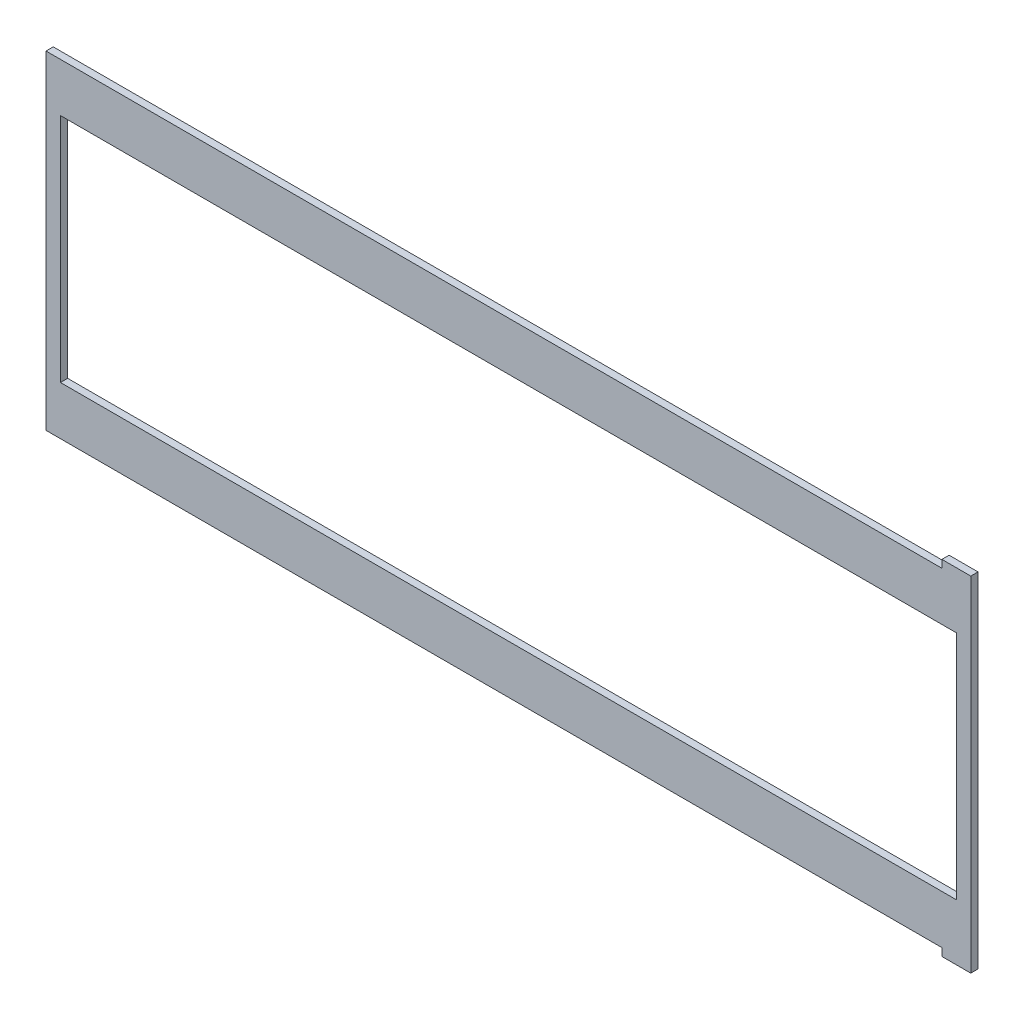
SolidWorks part; units mm, degrees
ref_plane "Front Plane" through (0, 0, 0) normal (0, 0, 1) x (1, 0, 0)
ref_plane "Top Plane" through (0, 0, 0) normal (0, 1, 0) x (1, 0, 0)
ref_plane "Right Plane" through (0, 0, 0) normal (1, 0, 0) x (0, 0, -1)
sketch "Sketch1" plane through (0, 0, 0) normal (0, 0, 1) x (1, 0, 0)
  line L0 (0, 72.1868) -> (406.4, 72.1868) construction
  line L1 (0, 0) -> (393.7, 0)
  line L2 (0, 0) -> (0, 144.3736)
  line L3 (0, 144.3736) -> (393.7, 144.3736)
  line L4 (406.4, 0) -> (406.4, 144.3736)
  line L6 (393.7, 144.3736) -> (393.7, 147.7518)
  line L7 (393.7, 147.7518) -> (406.4, 147.7518)
  line L8 (406.4, 144.3736) -> (406.4, 147.7518)
  line L9 (406.4, 0) -> (406.4, -3.3782)
  line L10 (393.7, -3.3782) -> (406.4, -3.3782)
  line L11 (393.7, 0) -> (393.7, -3.3782)
  line L13 (6.35, 122.9868) -> (400.05, 122.9868)
  line L14 (6.35, 122.9868) -> (6.35, 21.3868)
  line L15 (6.35, 21.3868) -> (400.05, 21.3868)
  line L16 (400.05, 122.9868) -> (400.05, 21.3868)
  point P17 (6.35, 72.1868)
  dimension "D1" = 406.4
  dimension "D2" = 144.3736
  dimension "D3" = 151.13
  dimension "D4" = 12.7
  dimension "D5" = 6.35
  dimension "D6" = 6.35
  dimension "D7" = 101.6
extrude "Boss-Extrude1" add sketch "Sketch1" along normal blind 3.175 contours L0 L2 L1 L11 L10 L4 L16 L15 L14 | L2 L0 L14 L13 L16 L4 L7 L6 L3 region at (204.1004, 131.2542, 0) region at (204.1004, 13.1194, 0)
equation "\"ROADWIDTH\"=5.684"
equation "\"TABWIDTH\"=5.95"
equation "\"D2@Sketch1\"=\"ROADWIDTH\""
equation "\"D3@Sketch1\"=\"TABWIDTH\""
